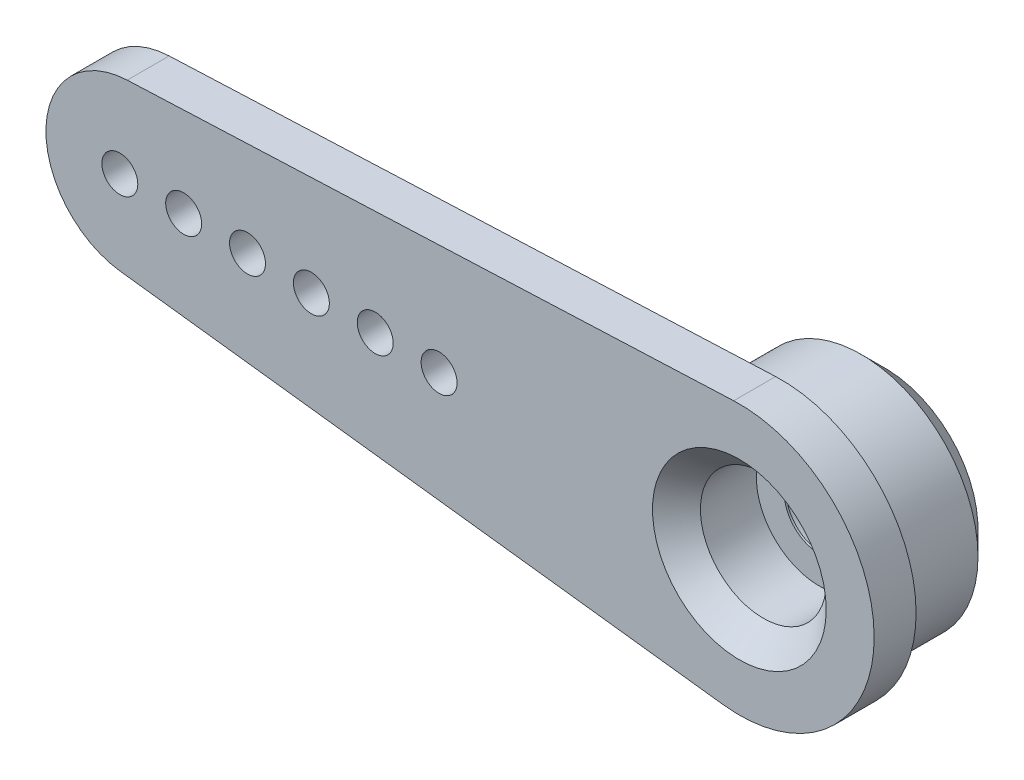
SolidWorks part; units mm, degrees
ref_plane "Plan de face" through (0, 0, 0) normal (0, 0, 1) x (1, 0, 0)
ref_plane "Plan de dessus" through (0, 0, 0) normal (0, 1, 0) x (1, 0, 0)
ref_plane "Plan de droite" through (0, 0, 0) normal (1, 0, 0) x (0, 0, -1)
sketch "Esquisse1" plane through (0, 0, 0) normal (0, 0, 1) x (1, 0, 0)
  line L0 (-0.179, 4.2462) -> (30.1914, 5.5266)
  line L1 (-0.5172, -4.2184) -> (29.6543, -7.9173)
  arc A0 (-0.179, 4.2462) -> (-0.5172, -4.2184) centre (0, 0) ccw
  arc A1 (29.6543, -7.9173) -> (30.1914, 5.5266) centre (30.4757, -1.2175) ccw
  dimension "D1" = 8.5
  dimension "D3" = 13.5
  dimension "D2" = 30.5
extrude "Extrusion1" add sketch "Esquisse1" along normal blind 2.1
sketch "Esquisse2" plane through (0, 0, 0) normal (0, 0, -1) x (-1, 0, 0)
  circle A0 centre (-30.4757, -1.2175) radius 5.85
  arc A1 (-30.1914, 5.5266) -> (-29.6543, -7.9173) centre (-30.4757, -1.2175) ccw construction
  dimension "D1" = 11.7
extrude "Extrusion2" add sketch "Esquisse2" along normal blind 5.2
sketch "Esquisse3" plane through (0, 0, -5.2) normal (0, 0, -1) x (-1, 0, 0)
  circle A0 centre (-30.4757, -1.2175) radius 1.75
  circle A1 centre (-30.4757, -1.2175) radius 5.85 construction
  dimension "D1" = 3.5
extrude "Extrusion3" cut sketch "Esquisse3" against normal through all
sketch "Esquisse4" plane through (0, 0, 2.1) normal (0, 0, 1) x (1, 0, 0)
  circle A0 centre (30.4757, -1.2175) radius 3.15
  arc A1 (29.6543, -7.9173) -> (30.1914, 5.5266) centre (30.4757, -1.2175) ccw construction
  dimension "D1" = 6.3
extrude "Extrusion4" cut sketch "Esquisse4" against normal blind 4
sketch "Esquisse5" plane through (0, 0, -5.2) normal (0, 0, -1) x (-1, 0, 0)
  circle A0 centre (-30.4757, -1.2175) radius 2.95
  circle A1 centre (-30.4757, -1.2175) radius 5.85 construction
  dimension "D1" = 5.9
extrude "Extrusion5" cut sketch "Esquisse5" against normal blind 3.2
chamfer "Chanfrein2" distance 1.2 angle 45 2 edges at (33.6257, -1.2175, 2.1) (24.6257, -1.2175, -5.2)
hole_wizard "Dégagement M21" positions "Esquisse3D1" profile "Esquisse6" hole size "M2" standard "ISO" end condition through all
sketch3d "Esquisse3D1"
  arc A0 (-0.179, 4.2462, 2.1) -> (-0.5172, -4.2184, 2.1) centre (0, 0, 2.1) ccw construction
  point P0 (-0.55, 0, 2.1)
  point P7 (0, 0, 6.35)
  dimension "D1" = 0.55
sketch "Esquisse6" plane through (-0.55, 0, 2.1) normal (1, 0, 0) x (0, -1, 0)
  line L0 (0, 0) -> (0, 7.3)
  line L1 (0, 7.3) -> (0.9, 7.3)
  line L2 (0.9, 7.3) -> (0.9, 0)
  line L5 (0.9, 0) -> (0, 0)
  line L11 (0, -6.35) -> (0, 107.95) construction
  dimension "Diamètre du perçage jusqu'au prochain" = 1.8
  dimension "Profondeur du perçage jusqu'au prochain" = 7.3
ref_point "Point1"
ref_point "Point2"
ref_point "Point3"
ref_plane "Plan1" through (-0.0008, -0.0215, 0) normal (0.0392, 0.9992, 0) x (-0.9992, 0.0392, 0)
ref_axis "Axe1" through (29.9228, -1.1958, 2.1) along (-0.9992, 0.0392, 0)
pattern_linear "Répétition linéaire1" count 6 spacing 3.2 along (0.9992, -0.0392, 0) of "Dégagement M21"
